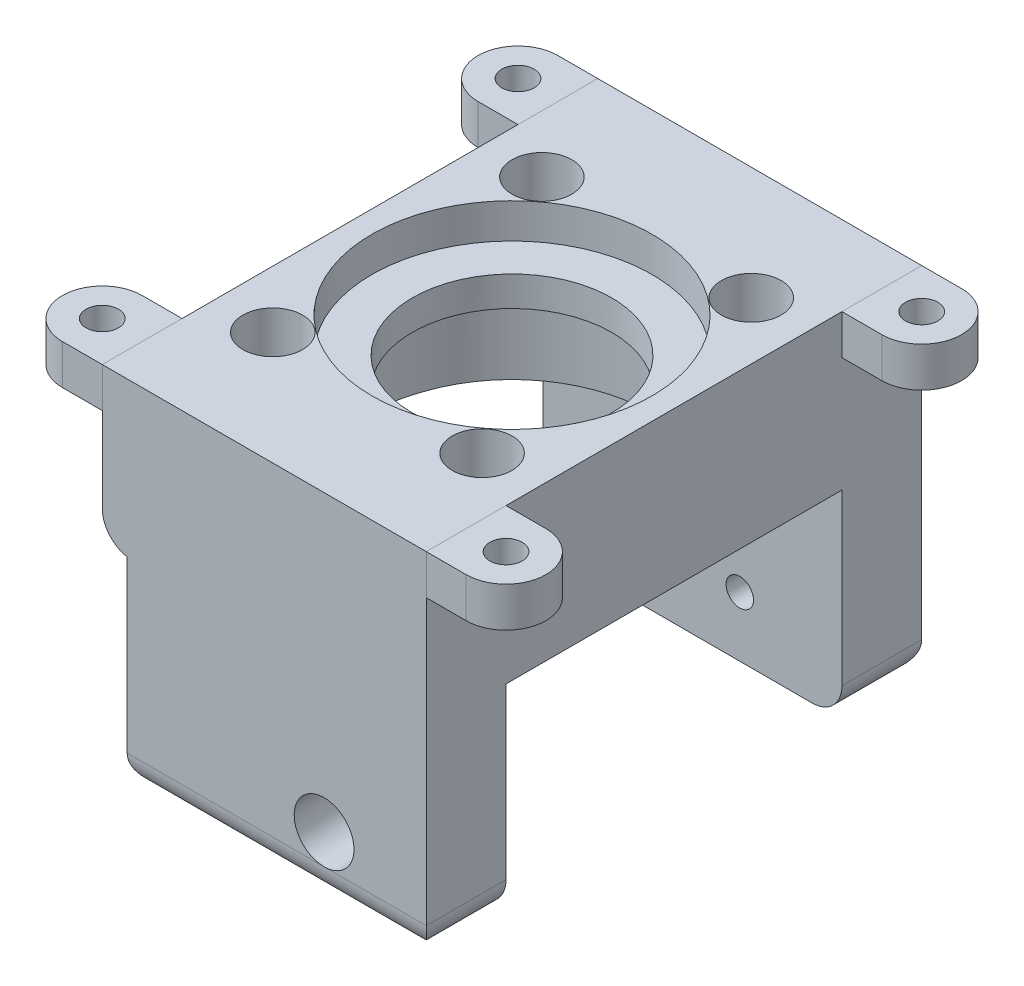
SolidWorks part; units mm, degrees
ref_plane "Front Plane" through (0, 0, 0) normal (0, 0, 1) x (1, 0, 0)
ref_plane "Top Plane" through (0, 0, 0) normal (0, 1, 0) x (1, 0, 0)
ref_plane "Right Plane" through (0, 0, 0) normal (1, 0, 0) x (0, 0, -1)
sketch "Sketch1" plane through (0, 0, 0) normal (0, 1, 0) x (1, 0, 0)
  line L1 (15, -16.85) -> (-15, -16.85)
  line L2 (15, -16.85) -> (15, 16.85)
  line L3 (15, 16.85) -> (-15, 16.85)
  line L4 (-15, -16.85) -> (-15, 16.85)
  line L5 (15, -16.85) -> (-15, 16.85) construction
  line L6 (15, 16.85) -> (-15, -16.85) construction
  circle A0 centre (-11.75, 13.5) radius 1.375
  circle A1 centre (-11.75, -13.5) radius 1.375
  circle A2 centre (9.25, -13.5) radius 1.4608
  circle A3 centre (9.25, 13.5) radius 1.4807
  circle A4 centre (-1.25, 0) radius 14
  point P0 (0, 0)
  dimension "D3" = 27
  dimension "D4" = 2.75
  dimension "D5" = 2.75
  dimension "D6" = 3.35
  dimension "D7" = 3.25
  dimension "D8" = 3.25
  dimension "D9" = 21
  dimension "D10" = 21
  dimension "D11" = 3.35
  dimension "D12" = 3.35
  dimension "D13" = 28
  dimension "D14" = 13.75
  dimension "D1" = 33.7
  dimension "D2" = 30
extrude "Boss-Extrude1" add sketch "Sketch1" along normal blind 15 contours A4 L4 L1 L2 L3 A3 A2 A1 A0 region at (0, 0, 16.3988)
sketch "Sketch2" plane through (0, 15, 0) normal (0, 1, 0) x (1, 0, 0)
  circle A0 centre (-1.25, 0) radius 14
  circle A1 centre (-1.25, 0) radius 10
  dimension "D1" = 20
extrude "Boss-Extrude2" add sketch "Sketch2" against normal blind 8
sketch "Sketch3" plane through (0, 15, 0) normal (0, 1, 0) x (1, 0, 0)
  circle A0 centre (-1.25, 0) radius 14
  circle A1 centre (-1.25, 0) radius 10
extrude "Cut-Extrude1" cut sketch "Sketch3" against normal blind 3
sketch "Sketch5" plane through (0, 15, 0) normal (0, 1, 0) x (1, 0, 0)
  line L1 (15, -16.85) -> (-15, -16.85)
  line L2 (15, -16.85) -> (15, 16.85)
  line L3 (15, 16.85) -> (-15, 16.85)
  line L4 (-15, -16.85) -> (-15, 16.85)
  line L5 (15, -16.85) -> (-15, 16.85) construction
  line L6 (15, 16.85) -> (-15, -16.85) construction
  circle A0 centre (-1.25, 0) radius 14
  circle A1 centre (-11.75, 13.5) radius 1.375
  circle A2 centre (9.25, 13.5) radius 1.4807
  circle A3 centre (9.25, -13.5) radius 1.4608
  circle A4 centre (-11.75, -13.5) radius 1.375
  point P3 (0, 0)
  arc M1 (-15, 2.6339) -> (-15, -2.6339) centre (-1.25, 0) cw
  line M2 (-15, -2.6339) -> (-15, -16.85)
  line M3 (-15, -16.85) -> (15, -16.85)
  line M4 (15, -16.85) -> (15, 16.85)
  line M5 (15, 16.85) -> (-15, 16.85)
  line M6 (-15, 16.85) -> (-15, 2.6339)
  circle M7 centre (9.25, 13.5) radius 1.4807
  circle M8 centre (9.25, -13.5) radius 1.4608
  circle M9 centre (-11.75, -13.5) radius 1.375
  circle M10 centre (-11.75, 13.5) radius 1.375
extrude "Boss-Extrude3" add sketch "Sketch5" along normal blind 0.5 contours M6 M1 M2 M3 M4 M5 M7 M9 M10 M8 region at (0, 15, 16.3988)
sketch "Sketch6" plane through (0, 15.5, 0) normal (0, 1, 0) x (1, 0, 0)
  line L0 (15, 16.85) -> (-15, 16.85) construction
  line L1 (-15, -16.85) -> (15, -16.85) construction
  line L3 (-3.5, 20.35) -> (3.5, 20.35)
  line L4 (-3.5, 20.35) -> (-3.5, -20.35)
  line L5 (-3.5, -20.35) -> (3.5, -20.35)
  line L6 (3.5, 20.35) -> (3.5, -20.35)
  circle A0 centre (0, 20.35) radius 1.625
  circle A1 centre (0, -20.35) radius 1.625
  circle A2 centre (0, 20.35) radius 3.5
  circle A3 centre (0, -20.35) radius 3.5
  line M8 (-15, -16.85) -> (15, -16.85)
  line M10 (15, 16.85) -> (-15, 16.85)
  dimension "D1" = 3.25
  dimension "D2" = 3.25
  dimension "D3" = 7
  dimension "D4" = 7
  dimension "D5" = 3.5
  dimension "D6" = 3.5
extrude "Boss-Extrude4" add sketch "Sketch6" against normal blind 5 contours L3 A2 A0 | A2 L3 A0 | A2 L6 M10 | A2 L4 M10 | A3 L4 M8 | A3 L6 M8 | L5 A3 A1 | L5 A3 A1 region at (0, 15.5, -22.0541) region at (0, 15.5, -18.6459) region at (2.7182, 15.5, -17.6318) region at (-2.7182, 15.5, -17.6318) region at (2.7182, 15.5, 17.6318) region at (0, 15.5, 22.0541) region at (0, 15.5, 18.6459) region at (-2.7182, 15.5, 17.6318)
sketch "Sketch7" plane through (0, 15.5, 0) normal (0, 1, 0) x (1, 0, 0)
  circle A0 centre (-11.75, 13.5) radius 3
  circle A1 centre (9.25, 13.5) radius 3
  circle A2 centre (9.25, -13.5) radius 3
  circle A3 centre (-11.75, -13.5) radius 3
  dimension "D1" = 6
  dimension "D2" = 6
  dimension "D3" = 6
  dimension "D4" = 6
extrude "Cut-Extrude2" cut sketch "Sketch7" against normal blind 12.5
sketch "Sketch8" plane through (0, 15.5, 0) normal (0, 1, 0) x (1, 0, 0)
  circle A0 centre (-1.25, 0) radius 14.05
  dimension "D1" = 28.1
extrude "Cut-Extrude3" cut sketch "Sketch8" against normal blind 3.5
sketch "Sketch9" plane through (0, 0, 0) normal (0, -1, 0) x (1, 0, 0)
  line L0 (-15, 16.85) -> (-15, 2.6339) construction
  line L1 (-15, 24.85) -> (15, 24.85)
  line L2 (-15, 24.85) -> (-15, -24.85)
  line L3 (-15, -24.85) -> (15, -24.85)
  line L4 (15, 24.85) -> (15, -24.85)
  line L5 (15, 16.85) -> (15, -16.85) construction
  line L6 (15, 16.85) -> (-15, 16.85) construction
  line L7 (15, -16.85) -> (-15, -16.85) construction
  line L9 (-15, 16.85) -> (15, 16.85)
  line L10 (-15, 16.85) -> (-15, -16.85)
  line L11 (-15, -16.85) -> (15, -16.85)
  line L12 (15, 16.85) -> (15, -16.85)
  line M7 (-15, -16.85) -> (15, -16.85)
  line M9 (15, 16.85) -> (-15, 16.85)
  dimension "D1" = 0
  dimension "D2" = 0
  dimension "D3" = 8
  dimension "D4" = 8
extrude "Boss-Extrude6" add sketch "Sketch9" along normal blind 20 separate body contours L4 L1 L2 M9 | L4 L2 L3 M7 region at (0, 0, 20.85) region at (0, 0, -20.85)
sketch "Sketch10" plane through (0, 0, 0) normal (0, 1, 0) x (1, 0, 0)
  line L1 (-15, 24.85) -> (15, 24.85)
  line L2 (-15, 24.85) -> (-15, 16.85)
  line L3 (-15, 16.85) -> (15, 16.85)
  line L4 (15, 24.85) -> (15, 16.85)
  line L5 (-15, -16.85) -> (15, -16.85)
  line L6 (-15, -16.85) -> (-15, -24.85)
  line L7 (-15, -24.85) -> (15, -24.85)
  line L8 (15, -16.85) -> (15, -24.85)
extrude "Boss-Extrude7" add sketch "Sketch10" along normal blind 15.5
sketch "Sketch11" plane through (0, 15.5, 0) normal (0, 1, 0) x (1, 0, 0)
  line L0 (-15, -24.85) -> (15, -24.85) construction
  line L1 (-15, 24.85) -> (-17.5, 24.85)
  line L2 (-15, 24.85) -> (-15, -24.85)
  line L3 (-15, -24.85) -> (-17.5, -24.85)
  line L4 (-17.5, 24.85) -> (-17.5, -24.85)
  circle A0 centre (-1.25, 0) radius 14.05
  dimension "D1" = 0
  dimension "D2" = 2.5
sketch "Sketch15" plane through (0, 0, 0) normal (0, -1, 0) x (1, 0, 0)
  line L1 (-17.5, 24.85) -> (-15, 24.85)
  line L2 (-17.5, 24.85) -> (-17.5, -24.85)
  line L3 (-17.5, -24.85) -> (-15, -24.85)
  line L4 (-15, 24.85) -> (-15, -24.85)
  circle A0 centre (-1.25, 0) radius 14
  line M3 (-15, 16.85) -> (-15, 2.6339)
  line M5 (-15, -2.6339) -> (-15, -16.85)
extrude "Boss-Extrude14" add sketch "Sketch15" against normal blind 15.5 contours A0 L4 L1 L2 L3 M3 M5 region at (-16.2582, 0, 0)
sketch "Sketch16" plane through (0, 12, 0) normal (0, 1, 0) x (1, 0, 0)
  circle A0 centre (-1.25, 0) radius 14.05
extrude "Cut-Extrude11" cut sketch "Sketch16" along normal blind 15.5
sketch "Sketch17" plane through (0, 15.5, 0) normal (0, 1, 0) x (1, 0, 0)
  line L0 (-17.5, -24.85) -> (-17.5, 24.85) construction
  line L1 (15, -24.85) -> (15, 24.85) construction
  line L2 (-17.5, -24.85) -> (15, -24.85) construction
  line L3 (15, 24.85) -> (-17.5, 24.85) construction
  line L4 (-21.5, 24.85) -> (19, 24.85)
  line L5 (-21.5, -24.85) -> (19, -24.85)
  line L6 (-21.5, 16.85) -> (19, 16.85)
  line L7 (-21.5, -16.85) -> (19, -16.85)
  circle A0 centre (-21.5, 20.85) radius 1.625
  circle A1 centre (19, 20.85) radius 1.625
  circle A2 centre (-21.5, -20.85) radius 1.625
  circle A3 centre (19, -20.85) radius 1.625
  circle A4 centre (-21.5, 20.85) radius 4
  circle A5 centre (-21.5, -20.85) radius 4
  circle A6 centre (19, -20.85) radius 4
  circle A7 centre (19, 20.85) radius 4
  line M4 (-17.5, 24.85) -> (-17.5, -24.85)
  line M6 (15, -24.85) -> (15, 24.85)
  dimension "D1" = 3.25
  dimension "D2" = 3.25
  dimension "D3" = 3.25
  dimension "D4" = 3.25
  dimension "D5" = 8
  dimension "D6" = 8
  dimension "D7" = 8
  dimension "D8" = 8
  dimension "D9" = 4
  dimension "D10" = 4
  dimension "D11" = 4
  dimension "D12" = 4
  dimension "D13" = 4
  dimension "D14" = 4
  dimension "D15" = 4
  dimension "D16" = 4
extrude "Boss-Extrude15" add sketch "Sketch17" against normal blind 4 separate body contours A4 A0 | A5 L7 M4 | A5 L5 M4 | A5 A2 | A6 L7 M6 | A6 A3 | A6 L5 M6 | A7 A1 | A7 L4 M6 | A7 L6 M6 | A4 L6 M4 | A4 L4 M4 region at (-18.3935, 15.5, -23.9565) region at (-18.7516, 15.5, -23.5984) region at (-18.3935, 15.5, -17.7435) region at (15.8935, 15.5, -23.9565) region at (21.7484, 15.5, -23.5984) region at (15.8935, 15.5, -17.7435) region at (-18.3935, 15.5, 17.7435) region at (15.8935, 15.5, 17.7435) region at (-18.7516, 15.5, 18.1016) region at (-18.3935, 15.5, 23.9565) region at (21.7484, 15.5, 18.1016) region at (15.8935, 15.5, 23.9565)
sketch "Sketch18" plane through (0, 0, -24.85) normal (0, 0, -1) x (-1, 0, 0)
  line L0 (15, 0) -> (-15, 0) construction
  line L2 (-15, 15.5) -> (-15, -20) construction
  circle A0 centre (-4.75, -14) radius 1.375
  dimension "D1" = 2.75
  dimension "D2" = 14
  dimension "D3" = 10.25
extrude "Cut-Extrude12" cut sketch "Sketch18" against normal blind 55.5
sketch "Sketch19" plane through (0, 0, 24.85) normal (0, 0, 1) x (1, 0, 0)
  circle A0 centre (4.75, -14) radius 3
  dimension "D1" = 6
extrude "Cut-Extrude13" cut sketch "Sketch19" against normal blind 5
sketch "Sketch20" plane through (0, 0, -24.85) normal (0, 0, -1) x (-1, 0, 0)
  circle A0 centre (-4.75, -14) radius 3
  dimension "D1" = 6
extrude "Cut-Extrude14" cut sketch "Sketch20" against normal blind 5
fillet "Fillet1" radius 3 1 edges at (-17.5, 0, 0)
fillet "Fillet2" radius 3 6 edges at (0, -20, 24.85) (0, -20, -24.85) (15, -20, 20.85) (15, -20, -20.85) (-15, -20, -20.85) (-15, -20, 20.85)
sketch "Sketch21" plane through (0, 7, 0) normal (0, -1, 0) x (1, 0, 0)
  circle A0 centre (-1.25, 0) radius 14
extrude "Cut-Extrude15" cut sketch "Sketch21" against normal blind 2
